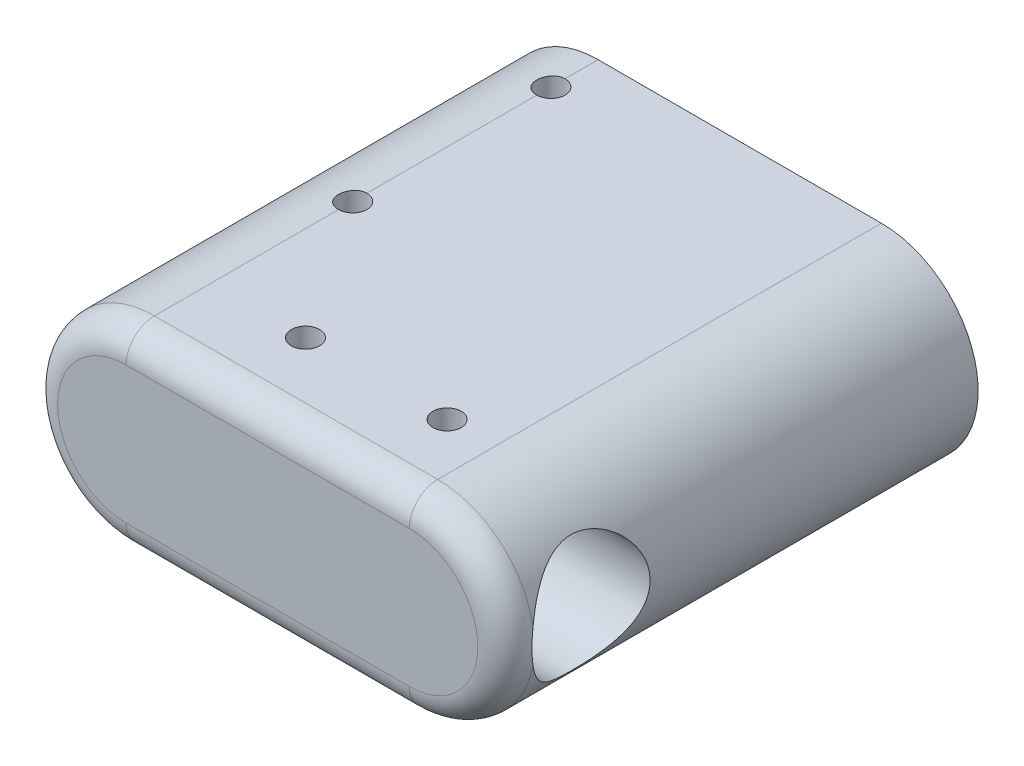
SolidWorks part; units mm, degrees
ref_plane "Front Plane" through (0, 0, 0) normal (0, 0, 1) x (1, 0, 0)
ref_plane "Top Plane" through (0, 0, 0) normal (0, 1, 0) x (1, 0, 0)
ref_plane "Right Plane" through (0, 0, 0) normal (1, 0, 0) x (0, 0, -1)
sketch "Sketch1" plane through (0, 0, 0) normal (0, 0, 1) x (1, 0, 0)
  line L0 (-73.6221, 11.8383) -> (106.3779, 11.8383)
  line L1 (-73.6221, -8.6617) -> (106.3779, -8.6617)
  line L2 (16.3779, 11.8383) -> (16.3779, -8.6617) construction
  circle A0 centre (-73.6221, 1.5883) radius 6.25
  circle A1 centre (-43.6221, 1.5883) radius 4.15
  arc A2 (-73.6221, 11.8383) -> (-73.6221, -8.6617) centre (-73.6221, 1.5883) ccw
  arc A3 (106.3779, 11.8383) -> (106.3779, -8.6617) centre (106.3779, 1.5883) cw
  circle A4 centre (76.3779, 1.5883) radius 4.15
  circle A5 centre (106.3779, 1.5883) radius 6.25
  dimension "D1" = 8.3
  dimension "D2" = 12.5
  dimension "D5" = 4
  dimension "D3" = 30
  dimension "D4" = 90
extrude "Boss-Extrude1" add sketch "Sketch1" along normal blind 50
sketch "Sketch2" plane through (0, 0, 50) normal (0, 0, 1) x (1, 0, 0)
  line L0 (106.3779, 11.8383) -> (-73.6221, 11.8383) construction
  line L1 (-73.6221, -8.6617) -> (106.3779, -8.6617) construction
  line L2 (-43.6221, 11.8383) -> (132.2063, 11.8383)
  line L3 (132.2063, 11.8383) -> (132.2063, -8.6617)
  line L4 (132.2063, -8.6617) -> (-43.6221, -8.6617)
  arc A0 (-43.6221, 11.8383) -> (-43.6221, -8.6617) centre (-43.6221, 1.5883) cw
extrude "Cut-Extrude1" cut sketch "Sketch2" against normal blind 127
sketch "Sketch3" plane through (0, 0, 50) normal (0, 0, 1) x (1, 0, 0)
  line L2 (-43.6221, 11.8383) -> (-73.6221, 11.8383)
  line L3 (-73.6221, -8.6617) -> (-43.6221, -8.6617)
  line L4 (-43.6221, 11.8383) -> (-73.6221, 11.8383)
  line L5 (-73.6221, -8.6617) -> (-43.6221, -8.6617)
  arc A2 (-43.6221, -8.6617) -> (-43.6221, 11.8383) centre (-43.6221, 1.5883) ccw
  arc A3 (-73.6221, 11.8383) -> (-73.6221, -8.6617) centre (-73.6221, 1.5883) ccw
  arc A4 (-43.6221, -8.6617) -> (-43.6221, 11.8383) centre (-43.6221, 1.5883) ccw
  arc A5 (-73.6221, 11.8383) -> (-73.6221, -8.6617) centre (-73.6221, 1.5883) ccw
  dimension "D1" = 0
extrude "Boss-Extrude2" add sketch "Sketch3" against normal blind 20
ref_plane "Plane1" through (-43.6221, 0, 0) normal (-1, 0, 0) x (0, 0, 1)
sketch "Sketch4" plane through (-43.6221, 0, 0) normal (-1, 0, 0) x (0, 0, 1)
  line L0 (41, 11.8383) -> (41, -8.6617) construction
  line L1 (50, 11.8383) -> (0, 11.8383) construction
  line L2 (0, -8.6617) -> (50, -8.6617) construction
  line L3 (50, -8.6617) -> (50, 11.8383) construction
  circle A0 centre (41, 1.5883) radius 6.25
  dimension "D1" = 12.5
  dimension "D2" = 9
extrude "Cut-Extrude2" cut sketch "Sketch4" against normal blind 20
sketch "Sketch5" plane through (-43.6221, 0, 0) normal (1, 0, 0) x (0, 0, -1)
  circle A0 centre (-41, 1.5883) radius 6.25
  dimension "D1" = 12.5
extrude "Cut-Extrude3" cut sketch "Sketch5" against normal blind 30
fillet "Fillet1" radius 3 4 edges at (-58.6221, 11.8383, 50) (-83.8721, 1.5883, 50) (-58.6221, -8.6617, 50) (-33.3721, 1.5883, 50)
sketch "Sketch6" plane through (0, 0, 30) normal (0, 0, -1) x (-1, 0, 0)
  circle A0 centre (73.6221, 1.5883) radius 4.5
  dimension "D1" = 9
extrude "Boss-Extrude3" add sketch "Sketch6" along normal blind 30
sketch "Sketch7" plane through (0, 11.8383, 0) normal (0, 1, 0) x (1, 0, 0)
  line L0 (-73.6221, -41) -> (-46.7331, -41) construction
  line L1 (-73.6221, -47) -> (-73.6221, 0) construction
  line L2 (-73.6221, -41) -> (-73.6221, 0) construction
  line L3 (-73.6221, -47) -> (-43.6221, -47) construction
  line L4 (-43.6221, 11.275) -> (-43.6221, -11.275) construction
  line L5 (-73.6221, 0) -> (-83.8721, 0) construction
  circle A0 centre (-48.6221, -41) radius 1.5
  circle A1 centre (-63.6221, -41) radius 1.5
  circle A2 centre (-73.6221, -26) radius 1.5
  circle A3 centre (-73.6221, -5) radius 1.5
  dimension "D2" = 3
  dimension "D1" = 6
  dimension "D3" = 5
  dimension "D4" = 5
  dimension "D5" = 15
  dimension "D6" = 10
extrude "Cut-Extrude4" cut sketch "Sketch7" against normal blind 30
sketch "Sketch8" plane through (0, -8.6617, 0) normal (0, -1, 0) x (-1, 0, 0)
  line L1 (73.6221, -8.1754) -> (76.3721, -6.5877)
  line L2 (76.3721, -6.5877) -> (76.3721, -3.4123)
  line L3 (76.3721, -3.4123) -> (73.6221, -1.8246)
  line L4 (73.6221, -1.8246) -> (70.8721, -3.4123)
  line L5 (70.8721, -3.4123) -> (70.8721, -6.5877)
  line L6 (70.8721, -6.5877) -> (73.6221, -8.1754)
  line L7 (73.6221, -29.1754) -> (76.3721, -27.5877)
  line L8 (76.3721, -27.5877) -> (76.3721, -24.4123)
  line L9 (76.3721, -24.4123) -> (73.6221, -22.8246)
  line L10 (73.6221, -22.8246) -> (70.8721, -24.4123)
  line L11 (70.8721, -24.4123) -> (70.8721, -27.5877)
  line L12 (70.8721, -27.5877) -> (73.6221, -29.1754)
  line L13 (63.6221, -44.1754) -> (66.3721, -42.5877)
  line L14 (66.3721, -42.5877) -> (66.3721, -39.4123)
  line L15 (66.3721, -39.4123) -> (63.6221, -37.8246)
  line L16 (63.6221, -37.8246) -> (60.8721, -39.4123)
  line L17 (60.8721, -39.4123) -> (60.8721, -42.5877)
  line L18 (60.8721, -42.5877) -> (63.6221, -44.1754)
  line L19 (48.6221, -44.1754) -> (51.3721, -42.5877)
  line L20 (51.3721, -42.5877) -> (51.3721, -39.4123)
  line L21 (51.3721, -39.4123) -> (48.6221, -37.8246)
  line L22 (48.6221, -37.8246) -> (45.8721, -39.4123)
  line L23 (45.8721, -39.4123) -> (45.8721, -42.5877)
  line L24 (45.8721, -42.5877) -> (48.6221, -44.1754)
  circle A0 centre (73.6221, -5) radius 2.75 construction
  circle A1 centre (73.6221, -26) radius 2.75 construction
  circle A2 centre (63.6221, -41) radius 2.75 construction
  circle A3 centre (48.6221, -41) radius 2.75 construction
  dimension "D1" = 5.5
extrude "Cut-Extrude5" cut sketch "Sketch8" against normal blind 2
sketch "Sketch9" plane through (0, 0, 0) normal (0, 0, -1) x (-1, 0, 0)
  circle A0 centre (73.6221, 1.5883) radius 4.5
extrude "Cut-Extrude6" cut sketch "Sketch9" against normal up to surface (30 mm away) up to face at (-69.1221, 1.5883, 30)
